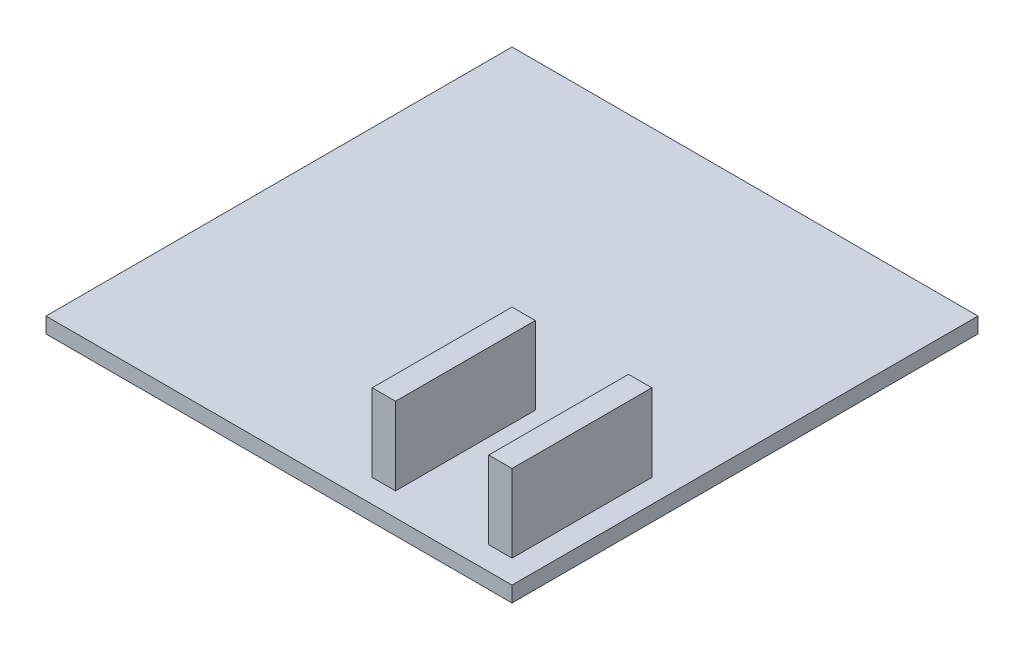
SolidWorks part; units mm, degrees
material "Pine"
ref_plane "Front Plane" through (0, 0, 0) normal (0, 0, 1) x (1, 0, 0)
ref_plane "Top Plane" through (0, 0, 0) normal (0, 1, 0) x (1, 0, 0)
ref_plane "Right Plane" through (0, 0, 0) normal (1, 0, 0) x (0, 0, -1)
sketch "Sketch3" plane through (0, 0, 0) normal (0, 1, 0) x (1, 0, 0)
  line L1 (-150, -150) -> (150, -150)
  line L2 (-150, -150) -> (-150, 150)
  line L3 (-150, 150) -> (150, 150)
  line L4 (150, -150) -> (150, 150)
  line L5 (-150, -150) -> (150, 150) construction
  line L6 (-150, 150) -> (150, -150) construction
  point P0 (0, 0)
  dimension "D1" = 300
  dimension "D2" = 300
extrude "Boss-Extrude1" add sketch "Sketch3" along normal blind 10
sketch "Sketch4" plane through (0, 10, 0) normal (0, 1, 0) x (1, 0, 0)
  line L0 (150, -150) -> (150, 150) construction
  line L1 (135, -135) -> (120, -135)
  line L2 (135, -135) -> (135, -45)
  line L3 (135, -45) -> (120, -45)
  line L4 (45, -135) -> (45, -45)
  line L5 (-150, -150) -> (150, -150) construction
  line L6 (60, -135) -> (60, -45)
  line L7 (120, -45) -> (120, -135)
  line L8 (60, -45) -> (45, -45)
  line L9 (60, -135) -> (45, -135)
  dimension "D1" = 15
  dimension "D2" = 15
  dimension "D3" = 90
  dimension "D4" = 90
  dimension "D5" = 15
  dimension "D6" = 15
extrude "Boss-Extrude2" add sketch "Sketch4" along normal blind 50
